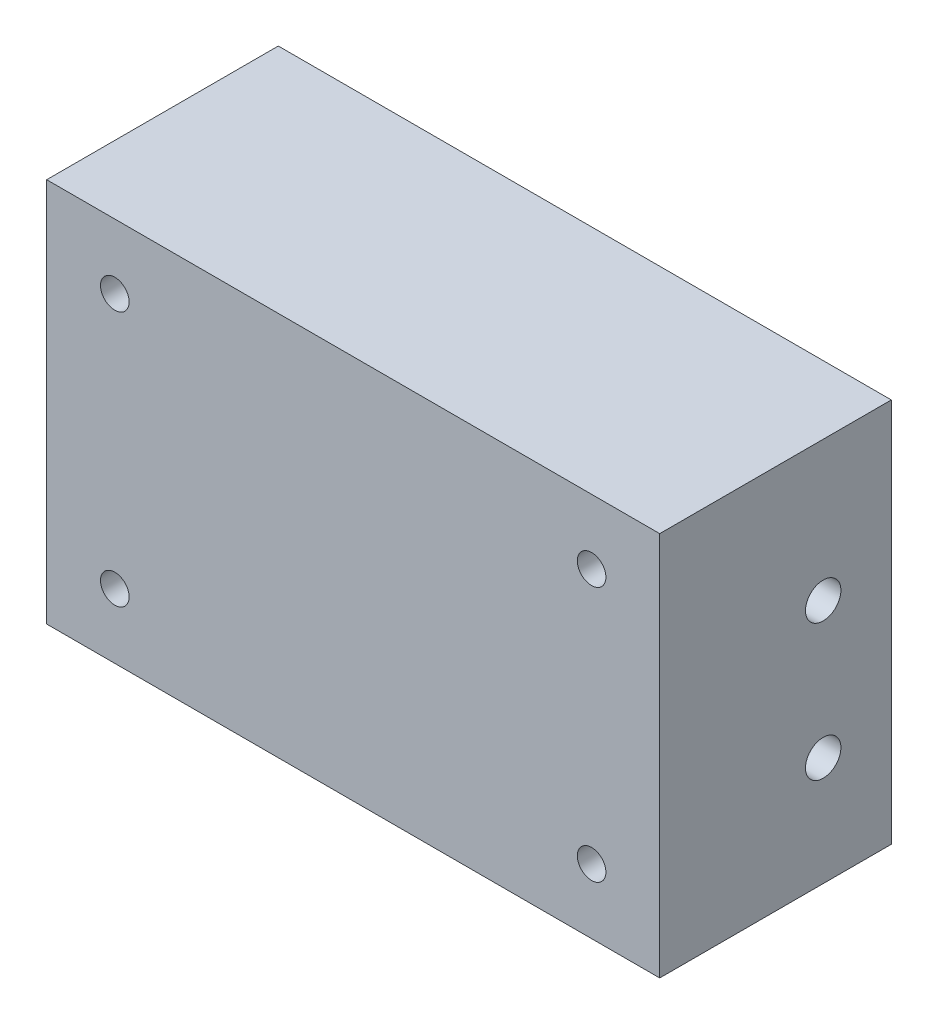
SolidWorks part; units mm, degrees
ref_plane "Front Plane" through (0, 0, 0) normal (0, 0, 1) x (1, 0, 0)
ref_plane "Top Plane" through (0, 0, 0) normal (0, 1, 0) x (1, 0, 0)
ref_plane "Right Plane" through (0, 0, 0) normal (1, 0, 0) x (0, 0, -1)
sketch "Sketch1" plane through (0, 0, 0) normal (0, 0, 1) x (1, 0, 0)
  line L0 (-52.07, 30.7975) -> (-52.07, -30.7975)
  line L1 (-57.15, -30.7975) -> (57.15, -30.7975)
  line L2 (-57.15, -30.7975) -> (-57.15, 30.7975)
  line L3 (-57.15, 30.7975) -> (57.15, 30.7975)
  line L4 (57.15, -30.7975) -> (57.15, 30.7975)
  line L5 (-57.15, -30.7975) -> (57.15, 30.7975) construction
  line L6 (-57.15, 30.7975) -> (57.15, -30.7975) construction
  line L7 (52.07, 30.7975) -> (52.07, -30.7975)
  line L8 (0, -1000) -> (0, 49000) construction
  circle A0 centre (-44.45, 23.8125) radius 2.667
  circle A3 centre (-44.45, -23.8125) radius 2.667
  circle A4 centre (44.45, -23.8125) radius 2.667
  circle A5 centre (44.45, 23.8125) radius 2.667
  point P0 (0, 0)
  dimension "D7" = 5.334
  dimension "D1" = 114.3
  dimension "D2" = 5.08
  dimension "D3" = 5.08
  dimension "D4" = 61.595
  dimension "D5" = 6.985
  dimension "D6" = 47.625
  dimension "D8" = 44.45
extrude "Boss-Extrude1" add sketch "Sketch1" along normal blind 5.08 contours L3 L2 L1 L0 | L7 L3 L0 L1 A4 A3 A0 A5 | L3 L7 L1 L4 region at (0, 0, 0) region at (-54.61, 0, 0) region at (54.61, 0, 0)
extrude "Boss-Extrude2" add sketch "Sketch1<3>" against normal blind 38.1 contours L3 L2 L1 L0 | L3 L7 L1 L4 region at (-54.61, 0, 0) region at (54.61, 0, 0)
sketch "Sketch1<3>" plane through (0, 0, 0) normal (0, 0, 1) x (1, 0, 0) same geometry as "Sketch1"
sketch "Sketch2" plane through (57.15, 0, 0) normal (1, 0, 0) x (0, 0, -1)
  line L0 (38.1, -30.7975) -> (38.1, 30.7975) construction
  line L1 (-5.08, -30.7975) -> (38.1, -30.7975) construction
  circle A0 centre (25.4, -15.5575) radius 3.302
  circle A1 centre (25.4, 9.8425) radius 3.302
  dimension "D1" = 6.604
  dimension "D2" = 25.4
  dimension "D3" = 12.7
  dimension "D4" = 15.24
extrude "Cut-Extrude1" cut sketch "Sketch2" against normal through all
sketch "Sketch3" plane through (0, 30.7975, 0) normal (0, 1, 0) x (1, 0, 0)
  line L1 (57.15, -5.08) -> (-57.15, -5.08)
  line L2 (57.15, -5.08) -> (57.15, 38.1)
  line L3 (57.15, 38.1) -> (-57.15, 38.1)
  line L4 (-57.15, -5.08) -> (-57.15, 38.1)
extrude "Boss-Extrude3" add sketch "Sketch3" along normal blind 5.08
extrude "Boss-Extrude4" add sketch "Sketch3<3>" against normal blind 5.08 from surface starting at face at (0, -30.7975, -17.78)
sketch "Sketch3<3>" plane through (0, 30.7975, 0) normal (0, 1, 0) x (1, 0, 0) same geometry as "Sketch3"
